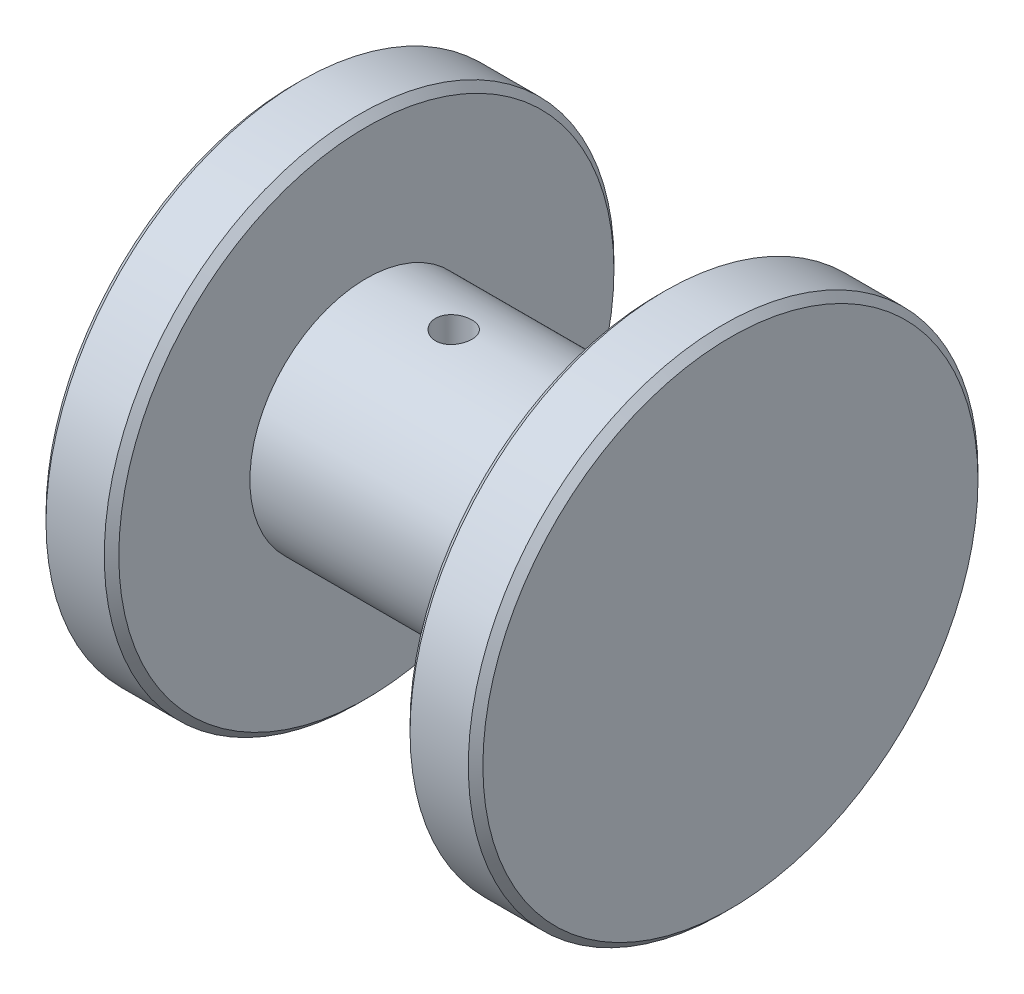
SolidWorks part; units mm, degrees
ref_plane "Front Plane" through (0, 0, 0) normal (0, 0, 1) x (1, 0, 0)
ref_plane "Top Plane" through (0, 0, 0) normal (0, 1, 0) x (1, 0, 0)
ref_plane "Right Plane" through (0, 0, 0) normal (1, 0, 0) x (0, 0, -1)
sketch "Sketch1" plane through (0, 0, 0) normal (0, 1, 0) x (1, 0, 0)
  line L0 (30, 0) -> (0, 0)
  line L1 (0, 17.5) -> (0, 0)
  line L6 (30, 17.5) -> (30, 0)
  line L7 (0, 17.5) -> (5, 17.5)
  line L8 (5, 17.5) -> (5, 8)
  line L9 (5, 8) -> (25, 8)
  line L10 (25, 8) -> (25, 17.5)
  line L11 (25, 17.5) -> (30, 17.5)
  dimension "D1" = 17.5
  dimension "D2" = 5
  dimension "D3" = 20
  dimension "D4" = 8
revolve "Revolve1" add sketch "Sketch1" angle 360 about L0
hole_wizard "Ø8.0mm Dowel Hole1" positions "Sketch3" profile "Sketch5" hole size "Ø8.0" standard "DIN"
sketch "Sketch3" plane through (0, 0, 0) normal (-1, 0, 0) x (0, 0, 1)
  point P0 (0, 0)
sketch "Sketch5" plane through (0, 0, 0) normal (0, 1, 0) x (0, 0, 1)
  line L0 (0, 0) -> (0, 20.4034)
  line L1 (0, 20.4034) -> (4, 18)
  line L2 (4, 18) -> (4, 0)
  line L5 (4, 0) -> (0, 0)
  line L10 (0, 20.4034) -> (-4, 18) construction
  line L11 (0, -6.35) -> (0, 107.95) construction
  dimension "Hole Dia." = 8
  dimension "Hole Depth" = 18
  dimension "Drill Angle" = 118
chamfer "Chamfer1" distance 0.5 angle 45 5 edges at (0, 0, 4) (30, 0, -17.5) (25, 0, -17.5) (5, 0, -17.5) (0, 0, -17.5)
hole_wizard "M3 Tapped Hole1" positions "3DSketch1" profile "Sketch8" tap size "M3" standard "DIN" end condition up to next
sketch3d "3DSketch1"
  line L0 (11, 8, 0) -> (5, 8, 0)
  circle A0 centre (5, 0, 0) radius 8 construction
  point P0 (11, 8, 0)
  point P9 (13, 0, 0)
  dimension "D1" = 6
sketch "Sketch8" plane through (11, 8, 0) normal (1, 0, 0) x (0, 0, 1)
  line L0 (0, 0) -> (0, 4)
  line L1 (0, 4) -> (1.25, 4)
  line L2 (1.25, 4) -> (1.25, 0)
  line L5 (1.25, 0) -> (0, 0)
  line L11 (0, -6.35) -> (0, 107.95) construction
  dimension "Thru Tap Drill Dia." = 2.5
  dimension "Thru Tap Drill Depth" = 4
cosmetic thread "Hole Thread1"
